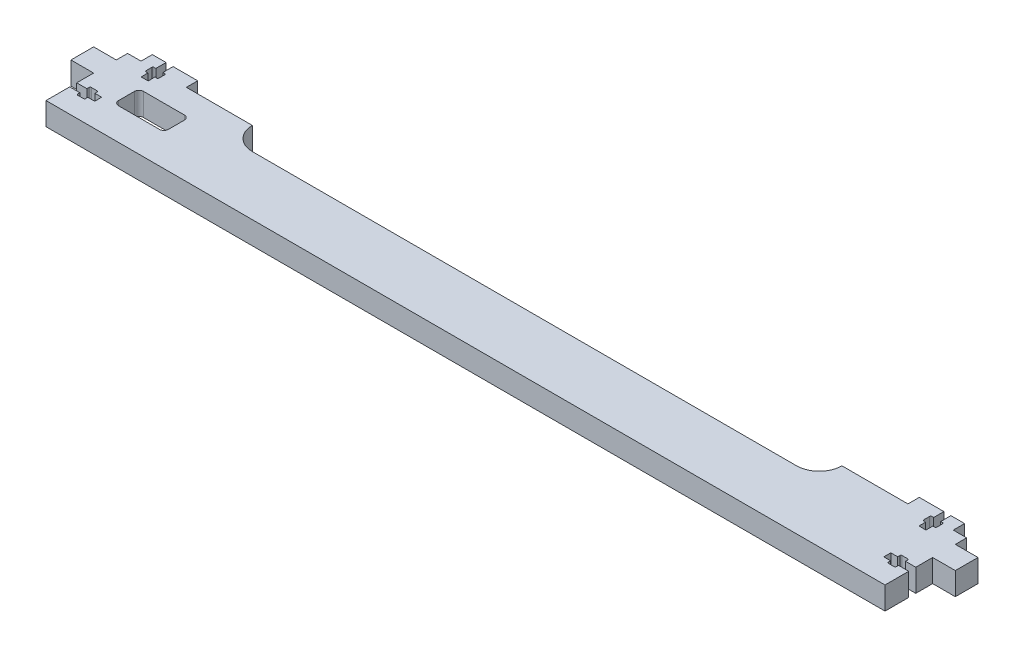
SolidWorks part; units mm, degrees
ref_plane "Front Plane" through (0, 0, 0) normal (0, 0, 1) x (1, 0, 0)
ref_plane "Top Plane" through (0, 0, 0) normal (0, 1, 0) x (1, 0, 0)
ref_plane "Right Plane" through (0, 0, 0) normal (1, 0, 0) x (0, 0, -1)
sketch "Sketch1" plane through (0, 0, 0) normal (0, 1, 0) x (1, 0, 0)
  line L0 (0, 18) -> (0, -18) construction
  line L1 (-185, 18) -> (0, 18)
  line L2 (-185, 18) -> (-185, 13)
  line L3 (-185, -18) -> (0, -18)
  line L4 (0, 18) -> (0, -18)
  line L5 (-185, 18) -> (0, 0) construction
  line L6 (-185, -18) -> (0, 0) construction
  line L7 (-185, 13) -> (-195, 13)
  line L8 (-195, 13) -> (-195, 3)
  line L9 (-195, 3) -> (-185, 3)
  line L10 (-185, 3) -> (-185, -18)
  point P0 (0, 0)
  dimension "D6" = 10
  dimension "D7" = 10
  dimension "D1" = 185
  dimension "D2" = 36
  dimension "D4" = 5
  dimension "D9" = 18
extrude "MainShape" add sketch "Sketch1" along normal blind 10 contours L2 L7 L8 L9 region at (-93.9423, 0, -0.1183)
sketch "Sketch15" plane through (0, 10, 0) normal (0, 1, 0) x (1, 0, 0)
  line L0 (-185, 18) -> (0, 18) construction
  line L1 (-159.1, 23) -> (-179.1, 23)
  line L2 (-159.1, 23) -> (-159.1, 13)
  line L3 (-159.1, 13) -> (-179.1, 13)
  line L4 (-179.1, 23) -> (-179.1, 13)
  line L5 (-159.1, 23) -> (-179.1, 13) construction
  line L6 (-159.1, 13) -> (-179.1, 23) construction
  line L7 (-185, 18) -> (-185, 13) construction
  point P0 (-169.1, 18)
  dimension "D1" = 20
  dimension "D2" = 5
  dimension "D3" = 15.9
extrude "Boss-Extrude4" add sketch "Sketch15" against normal through all
sketch "Sketch2" plane through (0, 10, 0) normal (0, 1, 0) x (1, 0, 0)
  line L0 (-171.5, 23) -> (-171.5, 12) construction
  line L2 (-173.05, 23) -> (-173.05, 18.5)
  line L3 (-173.05, 18.5) -> (-173.85, 18.5)
  line L4 (-174.35, 18) -> (-174.35, 15.5)
  line L5 (-173.85, 15) -> (-173.05, 15)
  line L6 (-173.05, 15) -> (-173.05, 12)
  line L7 (-173.05, 12) -> (-169.95, 12)
  line L8 (-185, 18) -> (-185, 13) construction
  line L9 (-173.05, 23) -> (-169.95, 23)
  line L10 (-169.95, 15) -> (-169.95, 12)
  line L11 (-169.15, 15) -> (-169.95, 15)
  line L12 (-168.65, 18) -> (-168.65, 15.5)
  line L13 (-169.95, 18.5) -> (-169.15, 18.5)
  line L14 (-169.95, 23) -> (-169.95, 18.5)
  line L16 (-185, -6) -> (-174, -6) construction
  line L17 (-159.1, 23) -> (-179.1, 23) construction
  line L50 (-185, 3) -> (-185, -18) construction
  line L51 (-174, -7.55) -> (-174, -4.45)
  line L52 (-174, -4.45) -> (-177, -4.45)
  line L53 (-177, -4.45) -> (-177, -3.5)
  line L54 (-177.5, -3) -> (-180, -3)
  line L55 (-180.5, -3.5) -> (-180.5, -4.45)
  line L56 (-180.5, -4.45) -> (-185, -4.45)
  line L57 (-185, -4.45) -> (-185, -7.55)
  line L58 (-195, 13) -> (-195, 3) construction
  line L59 (-180.5, -7.55) -> (-185, -7.55)
  line L60 (-180.5, -8.5) -> (-180.5, -7.55)
  line L61 (-177.5, -9) -> (-180, -9)
  line L62 (-177, -7.55) -> (-177, -8.5)
  line L63 (-174, -7.55) -> (-177, -7.55)
  arc A0 (-174.35, 15.5) -> (-173.85, 15) centre (-173.85, 15.5) ccw
  arc A1 (-173.85, 18.5) -> (-174.35, 18) centre (-173.85, 18) ccw
  arc A2 (-169.15, 18.5) -> (-168.65, 18) centre (-169.15, 18) cw
  arc A3 (-168.65, 15.5) -> (-169.15, 15) centre (-169.15, 15.5) cw
  arc A16 (-177, -3.5) -> (-177.5, -3) centre (-177.5, -3.5) ccw
  arc A17 (-180, -3) -> (-180.5, -3.5) centre (-180, -3.5) ccw
  arc A18 (-180, -9) -> (-180.5, -8.5) centre (-180, -8.5) cw
  arc A19 (-177, -8.5) -> (-177.5, -9) centre (-177.5, -8.5) cw
  point P14 (-174.35, 15)
  point P17 (-174.35, 18.5)
  point P28 (-168.65, 18.5)
  point P29 (-168.65, 15)
  point P34 (-195, 8)
  point P45 (-177, -3)
  point P48 (-180.5, -3)
  dimension "D8" = 0.5
  dimension "D16" = 0.5
  dimension "D1" = 11
  dimension "D2" = 1.55
  dimension "D3" = 1.55
  dimension "D5" = 2.85
  dimension "D6" = 3.5
  dimension "D7" = 13.5
  dimension "D9" = 11
  dimension "D10" = 8
  dimension "D11" = 3.5
  dimension "D12" = 3
  dimension "D13" = 1.55
  dimension "D14" = 1.55
  dimension "D15" = 14
  dimension "D4" = 8
extrude "ScrewSlots" cut sketch "Sketch2" against normal through all
mirror "Mirror1" about plane through (0, 0, 0) normal (1, 0, 0) of "Boss-Extrude4", "ScrewSlots", "MainShape"
sketch "Sketch6" plane through (0, 10, 0) normal (0, 1, 0) x (1, 0, 0)
  line L0 (0, -18) -> (0, -48) construction
  line L2 (-185, -18) -> (185, -18) construction
  line L3 (90, -48) -> (-90, -48)
  line L4 (-90, -48) -> (-120, -18)
  line L5 (90, -48) -> (120, -18)
  line L6 (-120, -18) -> (120, -18)
  dimension "D1" = 135
  dimension "D2" = 30
  dimension "D3" = 90
extrude "Boss-Extrude1" [suppressed] add sketch "Sketch6" against normal through all
sketch "Sketch8" plane through (0, 10, 0) normal (0, 1, 0) x (1, 0, 0)
  line L0 (-71.5, 4.8833) -> (-77.5, 4.8833) construction
  line L1 (-77, -1.6167) -> (-72, -1.6167)
  line L2 (-78, -0.6167) -> (-78, 4.3833)
  line L3 (-77, 5.3833) -> (-72, 5.3833)
  line L4 (-71, -0.6167) -> (-71, 4.3833)
  line L5 (-78, -1.6167) -> (-71, 5.3833) construction
  line L6 (-78, 5.3833) -> (-71, -1.6167) construction
  line L7 (-71.5, -1.1167) -> (-71.5, 4.8833) construction
  circle A0 centre (-74.5, -34.7667) radius 6.5
  circle A1 centre (-74.5, -15.8167) radius 5.5
  arc A2 (-77, -1.6167) -> (-78, -0.6167) centre (-77, -0.6167) cw
  circle A3 centre (-74.5, -34.7667) radius 6 construction
  circle A4 centre (-74.5, -15.8167) radius 3.5 construction
  arc A5 (-72, -1.6167) -> (-71, -0.6167) centre (-72, -0.6167) ccw
  arc A6 (-72, 5.3833) -> (-71, 4.3833) centre (-72, 4.3833) cw
  arc A7 (-78, 4.3833) -> (-77, 5.3833) centre (-77, 4.3833) cw
  point P6 (-74.5, 1.8833)
  dimension "D1" = 0.5
  dimension "D2" = 2
  dimension "D3" = 0.5
  dimension "D5" = 1
  dimension "D4" = 0.5
extrude "Cut-Extrude2" [suppressed] cut sketch "Sketch8" against normal through all
sketch "Sketch7" plane through (0, 10, 0) normal (0, 1, 0) x (1, 0, 0)
  circle A0 centre (60.5, -43.0167) radius 1.45
  circle A1 centre (-84.5, -43.0167) radius 1.45
  circle A2 centre (-84.5, 6.4833) radius 1.45
  circle A3 centre (60.5, 6.4833) radius 1.45
  dimension "D1" = 2.9
  dimension "D2" = 2.9
  dimension "D3" = 2.9
  dimension "D4" = 2.9
extrude "Cut-Extrude1" [suppressed] cut sketch "Sketch7" against normal through all
sketch "Sketch9" plane through (0, 10, 0) normal (0, 1, 0) x (1, 0, 0)
  line L0 (0, 7.2333) -> (0, -32.7667) construction
  line L1 (48.5, 7.2333) -> (-48.5, 7.2333) construction
  line L2 (-48.5, -32.7667) -> (48.5, -32.7667) construction
  line L3 (-48.5, -12.7667) -> (48.5, -12.7667) construction
  line L4 (-48.5, 7.2333) -> (-48.5, -32.7667) construction
  line L5 (48.5, -32.7667) -> (48.5, 7.2333) construction
  line L7 (-49, -33.2667) -> (49, -33.2667)
  line L8 (-49, -33.2667) -> (-49, 7.7333)
  line L9 (-49, 7.7333) -> (49, 7.7333)
  line L10 (49, -33.2667) -> (49, 7.7333)
  line L11 (-49, -33.2667) -> (49, 7.7333) construction
  line L12 (-49, 7.7333) -> (49, -33.2667) construction
  point P12 (0, -12.7667)
  dimension "D1" = 0.5
  dimension "D2" = 0.5
extrude "Cut-Extrude3" [suppressed] cut sketch "Sketch9" against normal through all and the other way through all
sketch "Sketch10" plane through (0, 10, 0) normal (0, 1, 0) x (1, 0, 0)
  line L0 (20, -39.2667) -> (20, -40.7667) construction
  line L1 (40, -39.2667) -> (0, -39.2667) construction
  line L2 (0, -40.7667) -> (40, -40.7667) construction
  line L3 (0, -40.0167) -> (40, -40.0167) construction
  line L4 (0, -39.2667) -> (0, -40.7667) construction
  line L5 (40, -40.7667) -> (40, -39.2667) construction
  line L7 (-0.2, -40.9667) -> (40.2, -40.9667)
  line L8 (-0.2, -40.9667) -> (-0.2, -39.0667)
  line L9 (-0.2, -39.0667) -> (40.2, -39.0667)
  line L10 (40.2, -40.9667) -> (40.2, -39.0667)
  line L11 (-0.2, -40.9667) -> (40.2, -39.0667) construction
  line L12 (-0.2, -39.0667) -> (40.2, -40.9667) construction
  point P12 (20, -40.0167)
  dimension "D1" = 0.2
  dimension "D2" = 0.2
extrude "Cut-Extrude4" [suppressed] cut sketch "Sketch10" against normal through all
sketch "Sketch12" [suppressed] plane through (0, 0, 0) normal (0, -1, 0) x (-1, 0, 0)
  line L1 (81.4, -9.8167) -> (67.6, -9.8167)
  line L2 (81.4, -9.8167) -> (81.4, -21.8167)
  line L3 (81.4, -21.8167) -> (67.6, -21.8167)
  line L4 (67.6, -9.8167) -> (67.6, -21.8167)
  line L5 (81.4, -9.8167) -> (67.6, -21.8167) construction
  line L6 (81.4, -21.8167) -> (67.6, -9.8167) construction
  point P0 (74.5, -15.8167)
  dimension "D1" = 13.8
  dimension "D2" = 12
extrude "PotentiometerAdjustment" [suppressed] cut sketch "Sketch12" against normal through all
sketch "Sketch11" plane through (0, 0, 0) normal (0, -1, 0) x (1, 0, 0)
  line L1 (-149, -7) -> (-167, -7)
  line L2 (-147, -5) -> (-147, 2)
  line L3 (-149, 4) -> (-167, 4)
  line L4 (-169, -5) -> (-169, 2)
  line L5 (-147, -7) -> (-169, 4) construction
  line L6 (-147, 4) -> (-169, -7) construction
  line L7 (173.05, -12) -> (169.95, -12) construction
  line L8 (-174, 7.55) -> (-174, 4.45) construction
  arc A0 (-147, 2) -> (-149, 4) centre (-149, 2) ccw
  arc A1 (-167, 4) -> (-169, 2) centre (-167, 2) ccw
  arc A2 (-167, -7) -> (-169, -5) centre (-167, -5) cw
  arc A3 (-149, -7) -> (-147, -5) centre (-149, -5) ccw
  point P0 (-158, -1.5)
  dimension "D3" = 2
  dimension "D1" = 22
  dimension "D2" = 11
  dimension "D4" = 5
  dimension "D5" = 5
extrude "LCDCableCutout" cut sketch "Sketch11" against normal through all
sketch "Sketch13" plane through (0, 10, 0) normal (0, 1, 0) x (1, 0, 0)
  line L0 (0, 18) -> (0, -18) construction
  line L1 (-169.95, 18) -> (169.95, 18) construction
  line L2 (-185, -18) -> (185, -18) construction
  line L3 (120, 18) -> (-120, 18) construction
  line L4 (120, 8) -> (-120, 8)
  line L5 (120, 28) -> (-120, 28)
  arc A0 (120, 8) -> (120, 28) centre (120, 18) ccw
  arc A1 (-120, 28) -> (-120, 8) centre (-120, 18) ccw
  point P8 (0, 18)
  dimension "D2" = 120
  dimension "D1" = 10
extrude "Cut-Extrude5" cut sketch "Sketch13" against normal through all
sketch "Sketch14" plane through (0, 10, 0) normal (0, 1, 0) x (1, 0, 0)
  line L1 (-169.95, 18) -> (169.95, 18) construction
  line L3 (-156.5, 18) -> (-156.5, 28) construction
  line L4 (-161.5, 18) -> (-151.5, 18)
  line L5 (-161.5, 18) -> (-161.5, 28)
  line L6 (-161.5, 28) -> (-151.5, 28)
  line L7 (-151.5, 18) -> (-151.5, 28)
  line L8 (-173.05, 12) -> (-169.95, 12) construction
  line L9 (154, 18) -> (154, 28) construction
  line L10 (149, 18) -> (149, 28)
  line L11 (159, 28) -> (149, 28)
  line L12 (159, 18) -> (159, 28)
  line L13 (159, 18) -> (149, 18)
  point P12 (-171.5, 12)
  dimension "D1" = 10
  dimension "D2" = 10
  dimension "D3" = 15
extrude "Boss-Extrude3" [suppressed] add sketch "Sketch14" against normal through all
equation "\"Y-ROD-SPACING\"=75"
equation "\"Y-BED-OFFSET\"=2"
equation "\"Y-BED-ROD-INSET\"=3.5"
equation "\"T-SLOT-NUT-FILLET-RADIUS\"=0.5"
equation "\"T-SLOT-SCREW-SHAFT-RADIUS\"=1.55"
equation "\"T-SLOT-SCREW-SHAFT-CUTOUT-LENGTH\"=11"
equation "\"T-SLOT-NUT-DEPTH\"=3.5"
equation "\"T-SLOT-NUT-WIDTH\"=2.85"
equation "\"T-SLOT-NUT-END-DISTANCE\"=8"
equation "\"ACRYLIC-TAB-CUTOUT-SIZE\"=\"ACRYLIC-THICKNESS\"+\"ACRYLIC-TAB-TOLERANCE\"*2"
equation "\"ACRYLIC-M3-HOLE\"=2.9"
equation "\"SMOOTHROD-CAP-SCREW-DISTANCE\"=20"
equation "\"D2@Sketch2\"=\"T-SLOT-SCREW-SHAFT-RADIUS\""
equation "\"D1@Sketch2\"=\"T-SLOT-SCREW-SHAFT-CUTOUT-LENGTH\""
equation "\"D6@Sketch2\"=\"T-SLOT-NUT-DEPTH\""
equation "\"D5@Sketch2\"=\"T-SLOT-NUT-WIDTH\""
equation "\"D3@Sketch2\"=\"T-SLOT-SCREW-SHAFT-RADIUS\""
equation "\"D8@Sketch2\"=\"T-SLOT-NUT-FILLET-RADIUS\""
equation "\"D4@Sketch2\"=\"T-SLOT-NUT-END-DISTANCE\""
equation "\"D11@Sketch2\"=\"T-SLOT-NUT-DEPTH\""
equation "\"D10@Sketch2\"=\"T-SLOT-NUT-END-DISTANCE\""
equation "\"D13@Sketch2\"=\"T-SLOT-SCREW-SHAFT-RADIUS\""
equation "\"D14@Sketch2\"=\"T-SLOT-SCREW-SHAFT-RADIUS\""
equation "\"D16@Sketch2\"=\"T-SLOT-NUT-FILLET-RADIUS\""
equation "\"D9@Sketch2\"=\"T-SLOT-SCREW-SHAFT-CUTOUT-LENGTH\""
equation "\"ACRYLIC-TAB-WIDTH\"=\"ACRYLIC-THICKNESS\""
equation "\"D6@Sketch1\"=\"ACRYLIC-TAB-WIDTH\""
equation "\"D7@Sketch1\"=\"ACRYLIC-TAB-WIDTH\""
equation "\"FRAME-WIDTH-INNER\"=370"
equation "\"D1@Sketch1\"=\"FRAME-WIDTH-INNER\"/2"
equation "\"X-ROD-SPACING\"=45"
equation "\"Z-ROD-SPACING\"=17.5"
equation "\"ACRYLIC-THICKNESS\"=10"
equation "\"ACRYLIC-THICKNESS2\"=4.5"
equation "\"NEMA17-HOLE-SPACING\"=31"
equation "\"NEMA17-CENTRAL-CUTOUT\"=22.5"
equation "\"Z-BRACKET-REACH\"=57"
equation "\"TOP-BRACKET-SPACING\"=40"
equation "\"SMOOTHROD-X-LENGTH\"=350"
equation "\"SMOOTHROD-Y-LENGTH\"=350"
equation "\"SMOOTHROD-Z-LENGTH\"=350"
equation "\"SMOOTHROD-TIGHTENING-HEADROOM\"=.25"
equation "\"LEADSCREW-Z-LENGTH\"=300"
equation "\"SCREW-LENGTH-FRAME\"=\"ACRYLIC-THICKNESS\" + 10"
equation "\"SCREW-HEAD-RADIUS\"=6"
equation "\"PRINTED-X-SMOOTHROD-DIAMETER\"=8.8"
equation "\"PRINTED-X-SMOOTHROD-CUTOUT\"=10"
equation "\"PRINTED-X-BASE-HEIGHT\"=10"
equation "\"PRINTED-LM8UU-CUTOUT-SIZE\"=15.5"
equation "\"PRINTED-LM8UU-CUTOUT-LENGTH\"=24.5"
equation "\"PRINTED-X-IDLER-HEIGHT\"=16"
equation "\"PSU-MOUNTING-WIDTH\"=95"
equation "\"PSU-MOUNTING-HEIGHT\"=177"
equation "\"D1@MainShape\"=\"ACRYLIC-THICKNESS\""
equation "\"Y-BELT-TO-ROD-DISTANCE\"=20"
equation "\"SPOOL-HOLDER-ROD-SPACING\"=150"
equation "\"Z-ROD-INSET\"=13.5"
equation "\"D7@Sketch2\"=\"Z-ROD-INSET\""
equation "\"D1@Sketch7\"=\"ACRYLIC-M3-HOLE\""
equation "\"D2@Sketch7\"=\"ACRYLIC-M3-HOLE\""
equation "\"D3@Sketch7\"=\"ACRYLIC-M3-HOLE\""
equation "\"D4@Sketch7\"=\"ACRYLIC-M3-HOLE\""
equation "\"Y-BED-SCREW-SPACING\"=209"
equation "\"Y-BED-SCREW-CUTOUT-SLOT-HEIGHT\"=2"
equation "\"ACRYLIC-TAB-TOLERANCE\"=-.05"
equation "\"SCREW-LENGTH-MOTOR\"=\"ACRYLIC-THICKNESS\" + 5"
equation "\"SCREW-LENGTH-EXTRUDER\"=28"
equation "\"PRINTED-M3-HOLE\"=3.5"
equation "\"PRINTED-M3-NUT-AF\"=6.25"
equation "\"ACRYLIC-X-CARRIAGE-WIDTH\"=55"
equation "\"ACRYLIC-X-CARRIAGE-HEIGHT\"=75"
equation "\"ACRYLIC-X-CARRIAGE-LM8UU-CUTOUT-WIDTH\"=24.25"
equation "\"ACRYLIC-X-CARRIAGE-LM8UU-CUTOUT-HEIGHT\"=11.0"
equation "\"ACRYLIC-X-CARRIAGE-SCREW-SPACING-X\"=15"
equation "\"ACRYLIC-X-CARRIAGE-SCREW-SPACING-Y\"=33"
equation "\"ACRYLIC-X-CARRIAGE-CENTER-TAB-SPACING\"=14"
equation "\"ACRYLIC-X-CARRIAGE-EXTRUDER-OFFSET\"=26"
equation "\"ACRYLIC-X-CARRIAGE-EXTRUDER-ANGLE\"=90"
equation "\"ACRYLIC-X-CARRIAGE-EXTRUDER-SHELF-DEPTH\"=\"ACRYLIC-X-CARRIAGE-EXTRUDER-OFFSET\" + 28"
equation "\"ACRYLIC-X-CARRIAGE-EXTRUDER-BRACE-SPACING\"=23"
equation "\"ACRYLIC-X-CARRIAGE-EXTRUDER-BRACE-TAB-OFFSET\"=20"
equation "\"ACRYLIC-X-CARRIAGE-EXTRUDER-BRACE-HEIGHT\"=35"
equation "\"ACRYLIC-X-CARRIAGE-EXTRUDER-BRACE-SCREW-SPACING\"=22"
equation "\"ACRYLIC-X-CARRIAGE-DUAL-WIDTH-MULTIPLIER\"=1.65"
equation "\"ACRYLIC-X-CARRIAGE-DUAL-HOTEND-SPACING\"=42"
equation "\"ACRYLIC-X-CARRIAGE-DUAL-WIDTH\"=75"
equation "\"ACRYLIC-X-CARRIAGE-DUAL-HOTEND-SEPARATION\"=36"
equation "\"ACRYLIC-X-CARRIAGE-DUAL-MOUNT-PLATE-DEPTH\"=75"
equation "\"ACRYLIC-X-CARRIAGE-DUAL-MOUNT-BRACE-WIDTH\"=33"
equation "\"ACRYLIC-X-CARRIAGE-DUAL-MOUNT-SCREW-WIDTH\"=40"
equation "\"BLOWER-FAN-WIDTH\"=15"
equation "\"D1@Sketch14\"=\"ACRYLIC-TAB-WIDTH\""
equation "\"D2@Sketch14\"=\"ACRYLIC-THICKNESS\""
equation "\"D3@Sketch15\"=\"Z-ROD-INSET\"+2.4"
